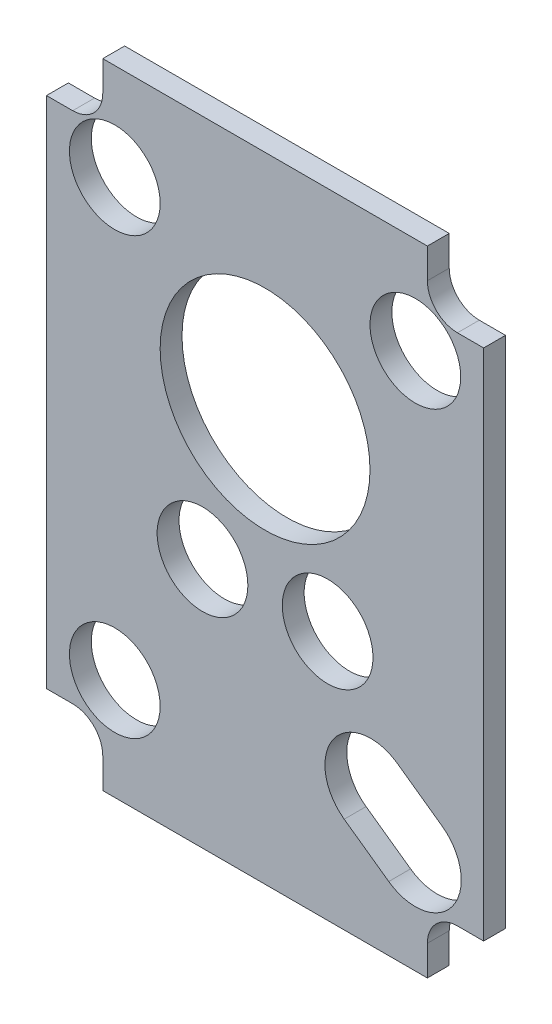
SolidWorks part; units mm, degrees
ref_plane "Front Plane" through (0, 0, 0) normal (0, 0, 1) x (1, 0, 0)
ref_plane "Top Plane" through (0, 0, 0) normal (0, 1, 0) x (1, 0, 0)
ref_plane "Right Plane" through (0, 0, 0) normal (1, 0, 0) x (0, 0, -1)
sketch "Sketch1" plane through (0, 0, 0) normal (0, 0, 1) x (1, 0, 0)
  line L0 (13.75, -19.7) -> (9.6769, -16.8) construction
  line L3 (-14.85, 26.25) -> (-14.85, 29)
  line L8 (17, -29) -> (-17, -29)
  line L9 (20, -26) -> (20, 26)
  line L10 (-17.6, 23.5) -> (-20, 23.5)
  line L11 (17, 29) -> (-17, 29)
  line L14 (-20, -26) -> (-20, 26)
  line L15 (20, -29) -> (-20, 29) construction
  line L16 (20, 29) -> (-20, -29) construction
  line L17 (11.314, -23.1214) -> (7.2409, -20.2214)
  line L18 (16.186, -16.2786) -> (12.1129, -13.3786)
  line L19 (0, -29) -> (0, 29) construction
  line L20 (14.85, 26.25) -> (14.85, 29)
  line L21 (17.6, 23.5) -> (20, 23.5)
  line L22 (17.6, -23.5) -> (20, -23.5)
  line L23 (14.85, -26.25) -> (14.85, -29)
  line L24 (-14.85, -26.25) -> (-14.85, -29)
  line L25 (-17.6, -23.5) -> (-20, -23.5)
  arc A14 (-17, -29) -> (-20, -26) centre (-17, -26) cw
  arc A15 (17, -29) -> (20, -26) centre (17, -26) ccw
  arc A16 (20, 26) -> (17, 29) centre (17, 26) ccw
  arc A17 (-17, 29) -> (-20, 26) centre (-17, 26) ccw
  circle A18 centre (-13.75, 20.15) radius 4.15
  circle A19 centre (13.75, 20.15) radius 4.15
  circle A20 centre (-13.75, -19.7) radius 4.15
  arc A21 (11.314, -23.1214) -> (16.186, -16.2786) centre (13.75, -19.7) ccw
  arc A22 (12.1129, -13.3786) -> (7.2409, -20.2214) centre (9.6769, -16.8) ccw
  circle A23 centre (0, 8.65) radius 9.6
  circle A24 centre (-5.725, -6.1) radius 4.15
  circle A25 centre (5.725, -6.1) radius 4.15
  circle A26 centre (-17.6, -26.25) radius 2.75
  circle A27 centre (17.6, -26.25) radius 2.75
  circle A28 centre (-17.6, 26.25) radius 2.75
  circle A29 centre (17.6, 26.25) radius 2.75
  point P0 (0, 0)
  point P14 (6.2555, -14.364)
  point P31 (11.7135, -18.25)
  point P37 (5.725, -10.25)
  dimension "D1" = 58
  dimension "D2" = 40
  dimension "D3" = 3
  dimension "D4" = 8.4
  dimension "D5" = 8.3
  dimension "D6" = 19.2
  dimension "D16" = 5.5
  dimension "D7" = 9.3
  dimension "D8" = 27.5
  dimension "D9" = 39.85
  dimension "D10" = 5
  dimension "D11" = 12.2
  dimension "D12" = 20.35
  dimension "D13" = 11.45
  dimension "D14" = 22.9
  dimension "D15" = 35.2
extrude "Boss-Extrude1" add sketch "Sketch1" along normal blind 2 contours A29 A16 L11 A17 A28 L14 A26 A14 L8 A15 A27 L9 A25 A24 A23 A22 L18 A21 L17 A20 A19 A18 region at (-14.1454, 27.625, 0)
